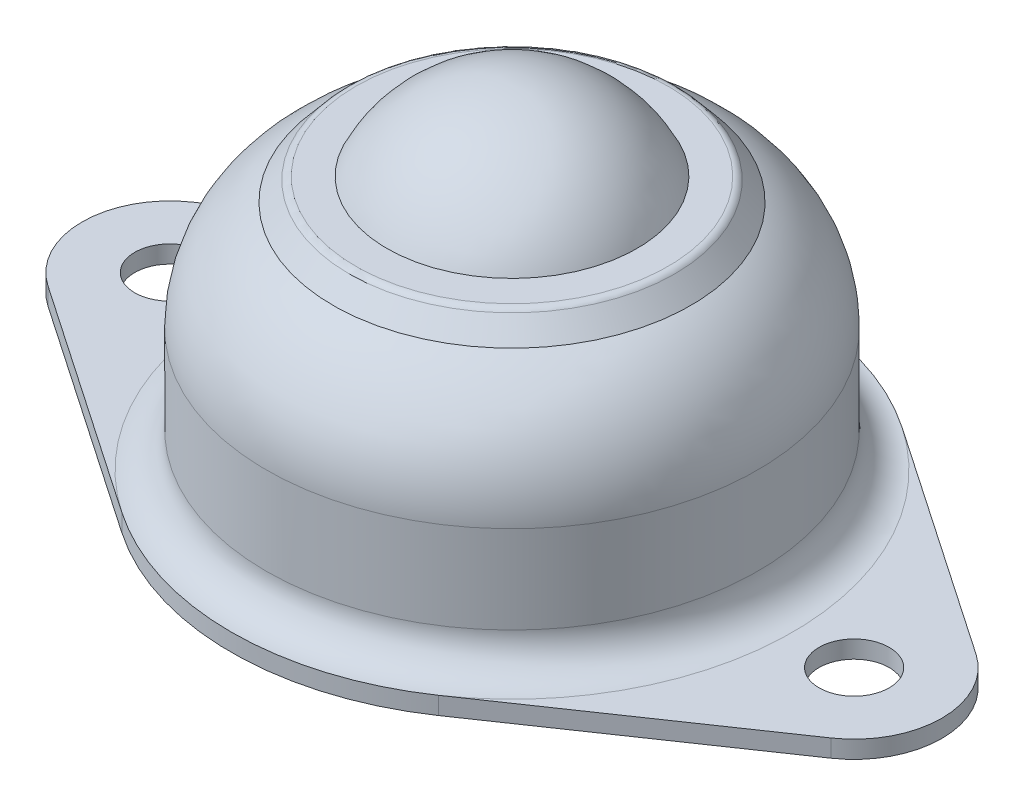
SolidWorks part; units mm, degrees
ref_plane "Front" through (0, 0, 0) normal (0, 0, 1) x (1, 0, 0)
ref_plane "Top" through (0, 0, 0) normal (0, 1, 0) x (1, 0, 0)
ref_plane "Right" through (0, 0, 0) normal (1, 0, 0) x (0, 0, -1)
sketch "草圖1" plane through (0, 0, 0) normal (0, 1, 0) x (1, 0, 0)
  line L0 (-19.5, 0) -> (19.5, 0) construction
  line L1 (-22.3205, 4.1285) -> (-9.0256, 13.2113)
  line L2 (9.0256, 13.2113) -> (22.3205, 4.1285)
  line L3 (-22.3205, -4.1285) -> (-9.0256, -13.2113)
  line L4 (9.0256, -13.2113) -> (22.3205, -4.1285)
  line L5 (0, -16) -> (0, 16) construction
  circle A0 centre (19.5, 0) radius 2
  circle A1 centre (-19.5, 0) radius 2
  arc A3 (-22.3205, 4.1285) -> (-22.3205, -4.1285) centre (-19.5, 0) ccw
  arc A4 (22.3205, -4.1285) -> (22.3205, 4.1285) centre (19.5, 0) ccw
  arc A5 (-9.0256, -13.2113) -> (9.0256, -13.2113) centre (0, 0) ccw
  arc A8 (9.0256, 13.2113) -> (-9.0256, 13.2113) centre (0, 0) ccw
  point P8 (0, 0)
  dimension "D1" = 4
  dimension "D2" = 4
  dimension "D4" = 16
  dimension "D5" = 10
  dimension "D6" = 10
  dimension "D7" = 16
  dimension "D3" = 39
extrude "填料-伸長1" add sketch "草圖1" along normal blind 1
sketch "草圖2" plane through (0, 0, 0) normal (0, 0, 1) x (1, 0, 0)
  line L0 (-14, 1) -> (-14, 8)
  line L1 (-22.3205, 1) -> (-9.0256, 1) construction
  line L3 (0, 20) -> (0, 1)
  line L4 (9.0256, 1) -> (-9.0256, 1) construction
  line L5 (0, 1) -> (-14, 1)
  line L6 (-7.1309, 15.5) -> (-8.8978, 15.5)
  line L7 (-9.2808, 15.3214) -> (-10.2002, 14.2256)
  arc A1 (-7.1309, 15.5) -> (0, 20) centre (0, 12.1) cw
  arc A3 (-14, 8) -> (-10.2002, 14.2256) centre (-7, 8) cw
  arc A4 (-8.8978, 15.5) -> (-9.2808, 15.3214) centre (-8.8978, 15) ccw
  point P14 (-9.1309, 15.5)
  dimension "D1" = 7.9
  dimension "D4" = 4.5
  dimension "D5" = 7
  dimension "D7" = 130
  dimension "D8" = 7
  dimension "D9" = 0.5
  dimension "D2" = 19
  dimension "D3" = 14
  dimension "D6" = 2
  dimension "D10" = 11.1
revolve "旋轉1" add sketch "草圖2" angle 360 about L3
fillet "圓角1" radius 2 1 edges at (0, 1, 14)
sketch "草圖3" plane through (0, 0, 0) normal (0, 0, 1) x (1, 0, 0)
  line L3 (0, 0) -> (-13, 0)
  line L6 (-22.3205, 0) -> (-9.0256, 0) construction
  line L7 (-13, 0) -> (-13, 7)
  line L11 (-13, 7) -> (-12.7, 7)
  line L13 (-9.0256, 1) -> (9.0256, 1) construction
  line L14 (0, 1) -> (0, 0)
  spline S0 degree 2 poles (-12.7, 7) (-8.5987, 1) (0, 1) knots 0 0 0 1 1 1
  dimension "D2" = 13
  dimension "D3" = 7
  dimension "D4" = 0.3
revolve "除料-旋轉1" cut sketch "草圖3" angle 360 about L14
fillet "圓角3" radius 2 1 edges at (-13, 0, 0)
